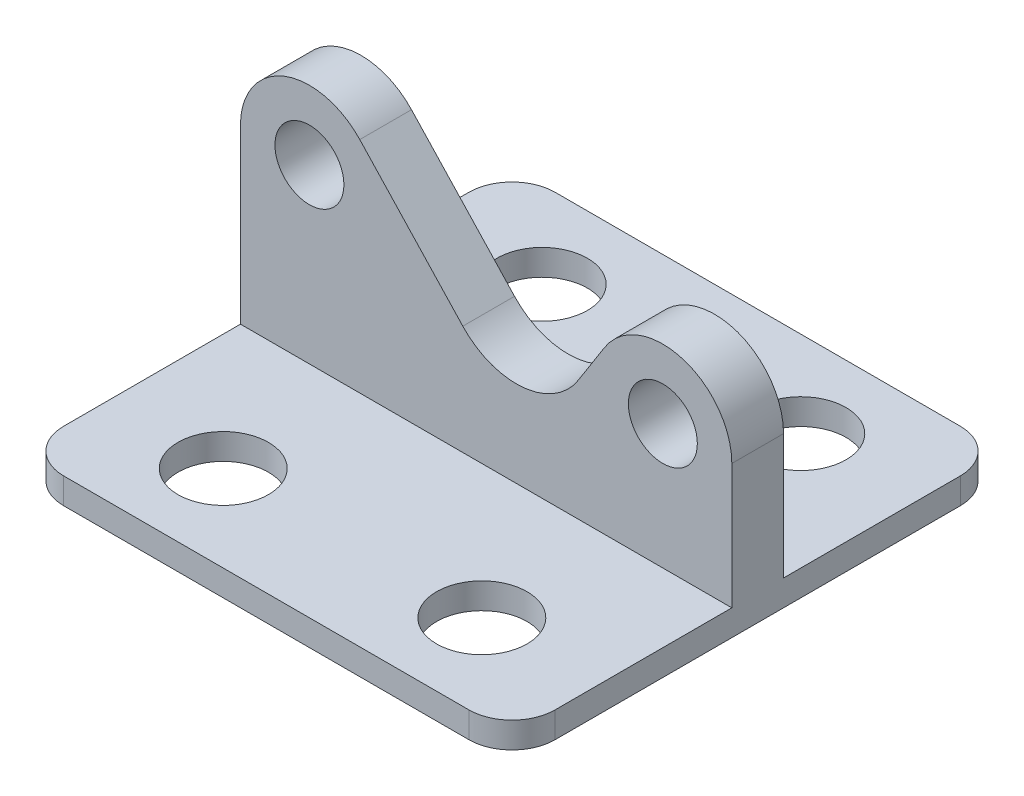
SolidWorks part; units mm, degrees
ref_plane "前视基准面" through (0, 0, 0) normal (0, 0, 1) x (1, 0, 0)
ref_plane "上视基准面" through (0, 0, 0) normal (0, 1, 0) x (1, 0, 0)
ref_plane "右视基准面" through (0, 0, 0) normal (1, 0, 0) x (0, 0, -1)
ref_plane "基准面1" through (0, 0, 0) normal (0, 0, 1) x (1, 0, 0)
sketch "草图1" plane through (0, 0, 0) normal (0, 0, 1) x (1, 0, 0)
  line L0 (0, 0) -> (57, 0)
  line L1 (57, 0) -> (57, 17.5)
  line L2 (42.243, 21.7829) -> (39.1793, 16.9494)
  line L3 (25.7933, 15.6925) -> (13.8416, 28.4659)
  line L4 (0, 23) -> (0, 0)
  arc A0 (57, 17.5) -> (42.243, 21.7829) centre (49, 17.5) ccw
  arc A1 (39.1793, 16.9494) -> (25.7933, 15.6925) centre (32, 21.5) cw
  arc A2 (13.8416, 28.4659) -> (0, 23) centre (8, 23) ccw
  circle A3 centre (49, 17.5) radius 4
  circle A4 centre (8, 23) radius 4
extrude "凸台-拉伸1" add sketch "草图1" against normal blind 3 and the other way blind 3
ref_plane "基准面2" through (0, 0, 0) normal (0, 1, 0) x (1, 0, 0)
sketch "草图2" plane through (0, 0, 0) normal (0, 1, 0) x (1, 0, 0)
  line L0 (5, -28.5) -> (52, -28.5)
  line L1 (57, -23.5) -> (57, 23.5)
  line L2 (52, 28.5) -> (5, 28.5)
  line L3 (0, 23.5) -> (0, -23.5)
  arc A0 (0, -23.5) -> (5, -28.5) centre (5, -23.5) ccw
  arc A1 (52, -28.5) -> (57, -23.5) centre (52, -23.5) ccw
  arc A2 (57, 23.5) -> (52, 28.5) centre (52, 23.5) ccw
  arc A3 (5, 28.5) -> (0, 23.5) centre (5, 23.5) ccw
  circle A4 centre (43.5, -18.5) radius 5.25
  circle A5 centre (43.5, 18.5) radius 5.25
  circle A6 centre (13.5, -18.5) radius 5.25
  circle A7 centre (13.5, 18.5) radius 5.25
extrude "凸台-拉伸2" add sketch "草图2" along normal blind 3
ref_plane "基准面3" through (0, 0, 0) normal (0, 0, 1) x (1, 0, 0)
ref_plane "基准面4" through (0, 0, 0) normal (0, 1, 0) x (1, 0, 0)
ref_plane "cp1 XY" through (0, 0, 0) normal (0, 0, 1) x (1, 0, 0)
ref_plane "cp1 XZ" through (0, 23, 0) normal (0, -1, 0) x (-1, 0, 0)
ref_plane "cp1 YZ" through (8, 0, 0) normal (1, 0, 0) x (0, 0, -1)
ref_axis "cp1 X" through (-80.9, 23, 0) along (1, 0, 0)
ref_axis "cp1 Y" through (8, -50, 0) along (0, 1, 0)
ref_axis "cp1 Z" through (8, 23, 80.9) along (0, 0, -1)
sketch3d "cp1"
  point P0 (8, 23, 0)
ref_plane "cp2 XY" through (0, 0, 0) normal (0, 0, 1) x (1, 0, 0)
ref_plane "cp2 XZ" through (0, 17.5, 0) normal (0, -1, 0) x (-1, 0, 0)
ref_plane "cp2 YZ" through (49, 0, 0) normal (1, 0, 0) x (0, 0, -1)
ref_axis "cp2 X" through (-80.9, 17.5, 0) along (1, 0, 0)
ref_axis "cp2 Y" through (49, -50, 0) along (0, 1, 0)
ref_axis "cp2 Z" through (49, 17.5, 80.9) along (0, 0, -1)
sketch3d "cp2"
  point P0 (49, 17.5, 0)
ref_plane "cp XY" through (0, 0, 0) normal (0, 1, 0) x (1, 0, 0)
ref_plane "cp XZ" through (0, 0, 0) normal (0, 0, 1) x (1, 0, 0)
ref_plane "cp YZ" through (0, 0, 0) normal (1, 0, 0) x (0, 0, -1)
ref_axis "cp X" through (-80.9, 0, 0) along (1, 0, 0)
ref_axis "cp Y" through (0, 0, 50) along (0, 0, -1)
ref_axis "cp Z" through (0, 50, 0) along (0, -1, 0)
sketch3d "cp"
  point P0 (0, 0, 0)
equation "\"零件重量\"= \"SW-质量\""
